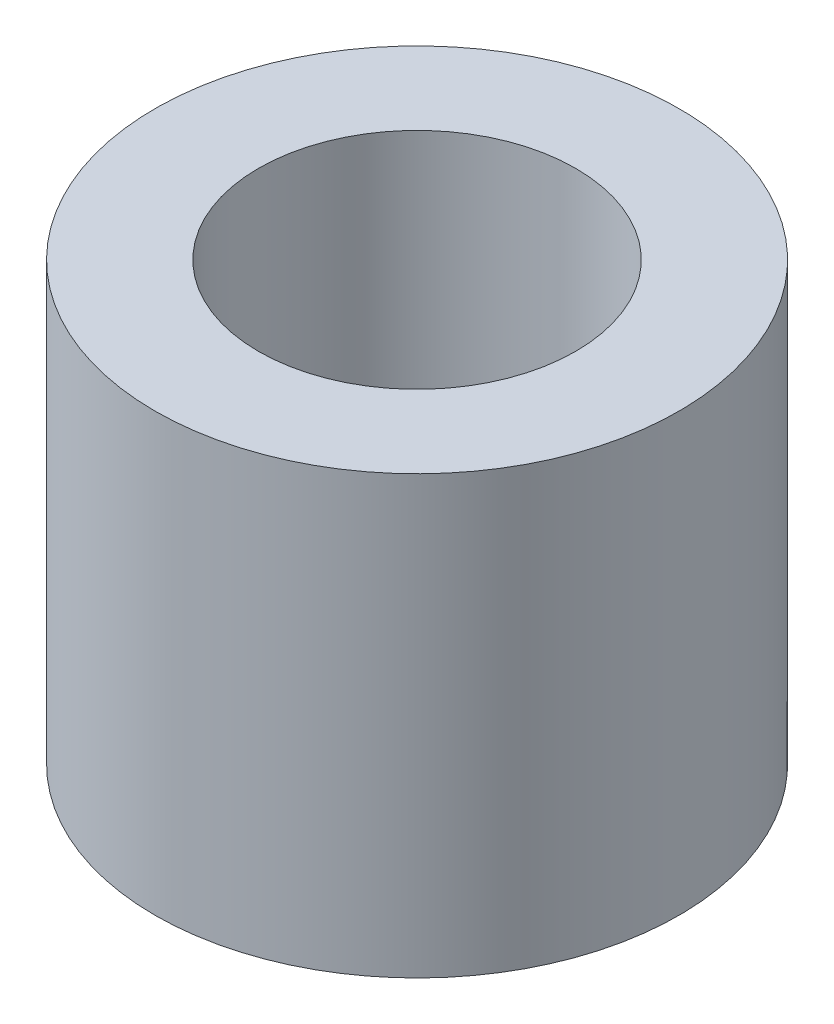
SolidWorks part; units mm, degrees
material "6063-T6"
ref_plane "Front Plane" through (0, 0, 0) normal (0, 0, 1) x (1, 0, 0)
ref_plane "Top Plane" through (0, 0, 0) normal (0, 1, 0) x (1, 0, 0)
ref_plane "Right Plane" through (0, 0, 0) normal (1, 0, 0) x (0, 0, -1)
sketch "Sketch1" plane through (0, 0, 0) normal (0, 1, 0) x (1, 0, 0)
  circle A0 centre (0, 0) radius 15
  circle A1 centre (0, 0) radius 2.5
  point P5 (0, 0)
  dimension "D1" = 30
  dimension "D2" = 5
extrude "Boss-Extrude1" add sketch "Sketch1" along normal blind 25
hole_wizard "G1/4 Tapped Hole1" positions "Sketch2" profile "Sketch4" tap size "G1/4" standard "ISO"
sketch "Sketch2" plane through (0, 25, 0) normal (0, 1, 0) x (1, 0, 0)
  point P0 (0, 0)
sketch "Sketch4" plane through (0, 25, 0) normal (1, 0, 0) x (0, 0, 1)
  line L0 (0, 0) -> (0, 18.5451)
  line L1 (0, 18.5451) -> (5.9, 15)
  line L2 (5.9, 15) -> (5.9, 0)
  line L5 (5.9, 0) -> (0, 0)
  line L10 (0, 18.5451) -> (-5.9, 15) construction
  line L11 (0, -6.35) -> (0, 107.95) construction
  dimension "Tap Drill Dia." = 11.8
  dimension "Tap Drill Depth" = 15
  dimension "Drill Angle" = 118
cosmetic thread "Hole Thread1" parameters "D1"=25, "D2"=13.157
sketch "Sketch14" plane through (0, 0, 0) normal (0, -1, 0) x (1, 0, 0)
  circle A0 centre (0, 0) radius 8.75
  dimension "D1" = 17.5
hole_wizard "G1/4 Tapped Hole2" positions "Sketch15" profile "Sketch16" tap size "G1/4" standard "ISO"
sketch "Sketch15" plane through (0, 0, 0) normal (0, -1, 0) x (-1, 0, 0)
  point P0 (0, 0)
sketch "Sketch16" plane through (0, 0, 0) normal (1, 0, 0) x (0, 0, -1)
  line L0 (0, 0) -> (0, 13.5451)
  line L1 (0, 13.5451) -> (5.9, 10)
  line L2 (5.9, 10) -> (5.9, 0)
  line L5 (5.9, 0) -> (0, 0)
  line L10 (0, 13.5451) -> (-5.9, 10) construction
  line L11 (0, -6.35) -> (0, 107.95) construction
  dimension "Tap Drill Dia." = 11.8
  dimension "Tap Drill Depth" = 10
  dimension "Drill Angle" = 118
cosmetic thread "Hole Thread2" parameters "D1"=10, "D2"=13.157
sketch "Sketch11" plane through (0, 25, 0) normal (0, 1, 0) x (1, 0, 0)
  circle A0 centre (0, 0) radius 9.0785
  dimension "D1" = 18.157
extrude "Cut-Extrude3" cut sketch "Sketch11" against normal blind 15 contours A0
